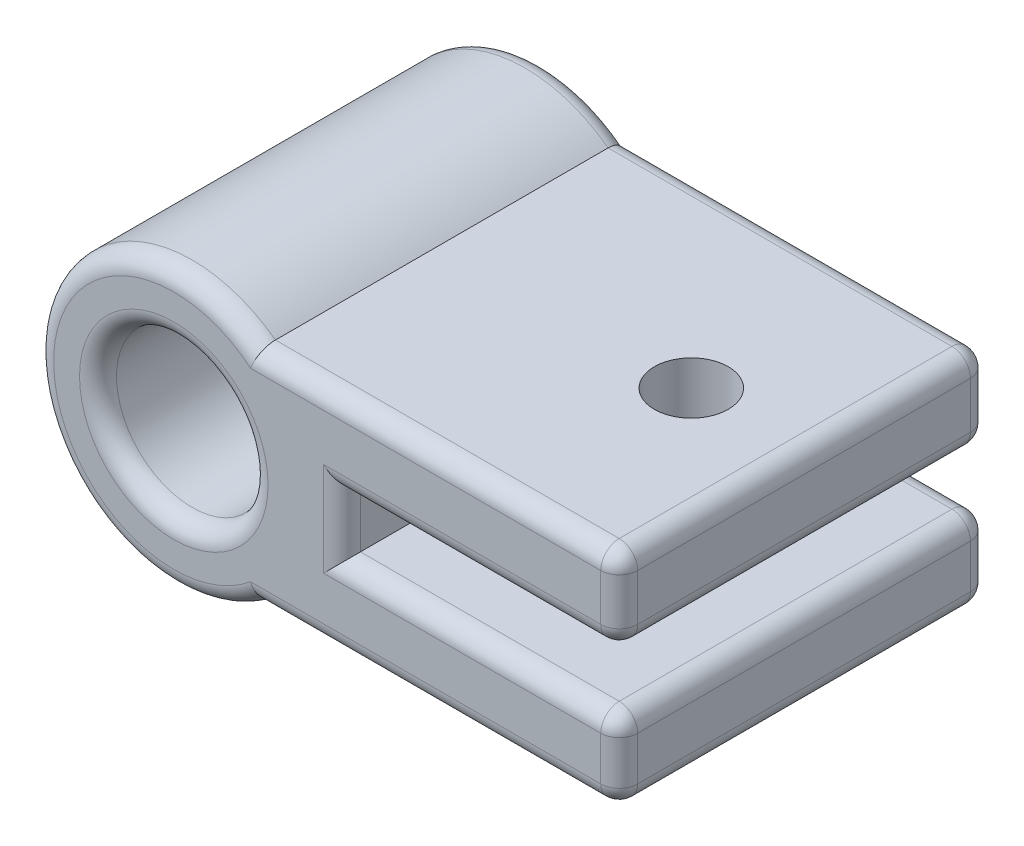
SolidWorks part; units mm, degrees
material "黄铜"
ref_plane "前视基准面" through (0, 0, 0) normal (0, 0, 1) x (1, 0, 0)
ref_plane "上视基准面" through (0, 0, 0) normal (0, 1, 0) x (1, 0, 0)
ref_plane "右视基准面" through (0, 0, 0) normal (1, 0, 0) x (0, 0, -1)
sketch "草图1" plane through (0, 0, 0) normal (0, 0, 1) x (1, 0, 0)
  circle A0 centre (0, 0) radius 7.5
  circle A1 centre (0, 0) radius 4.1
  dimension "D1" = 8.2
  dimension "D2" = 15
extrude "凸台-拉伸1" add sketch "草图1" along normal blind 20
sketch "草图2" plane through (0, 0, 0) normal (0, 1, 0) x (1, 0, 0)
  line L1 (4.1, 0) -> (24.1, 0)
  line L2 (4.1, 0) -> (4.1, -20)
  line L3 (4.1, -20) -> (24.1, -20)
  line L4 (24.1, 0) -> (24.1, -20)
  circle A0 centre (18, -10) radius 2
  point P8 (24.1, -10)
  dimension "D3" = 4
  dimension "D4" = 18
  dimension "D1" = 20
  dimension "D2" = 0
  dimension "D5" = 20
extrude "凸台-拉伸2" add sketch "草图2" along normal blind 6 and the other way blind 6
sketch "草图3" plane through (24.1, 0, 0) normal (1, 0, 0) x (0, 0, -1)
  line L0 (-20, -6) -> (-20, 6) construction
  line L1 (-20, 1.4729) -> (0, 1.4729)
  line L2 (-20, 1.4729) -> (-20, -1.6271)
  line L3 (-20, -1.6271) -> (0, -1.6271)
  line L4 (0, 1.4729) -> (0, -1.6271)
  line L5 (0, -6) -> (0, 6) construction
  dimension "D1" = 3.1
extrude "切除-拉伸1" cut sketch "草图3" against normal blind 15
fillet "圆角1" radius 1 22 edges at (24.1, -6, 10) (24.1, -1.6271, 10) (24.1, 6, 10) (24.1, 1.4729, 10) (4.1, 0, 0) (14.3, 6, 0) (-7.5, 0, 0) (14.3, -6, 0) (24.1, -3.8136, 0) (16.6, -1.6271, 0) (9.1, -0.0771, 0) (16.6, 1.4729, 0) (24.1, 3.7364, 0) (4.1, 0, 20) (9.1, -0.0771, 20) (16.6, -1.6271, 20) (24.1, -3.8136, 20) (14.3, -6, 20) (-7.5, 0, 20) (14.3, 6, 20) (24.1, 3.7364, 20) (16.6, 1.4729, 20)
